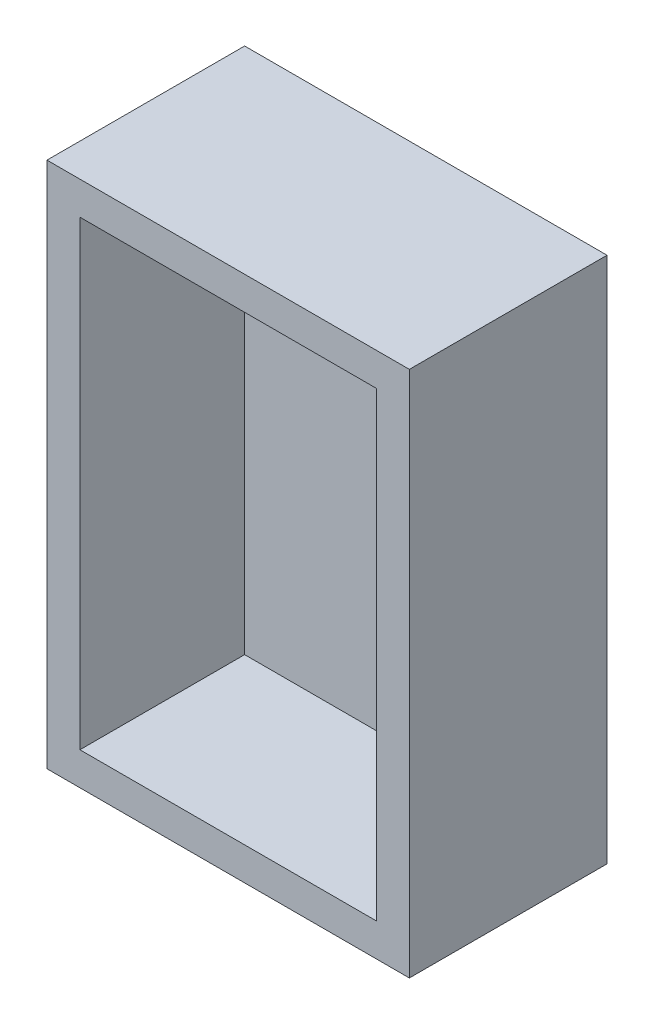
SolidWorks part; units mm, degrees
ref_plane "Front Plane" through (0, 0, 0) normal (0, 0, 1) x (1, 0, 0)
ref_plane "Top Plane" through (0, 0, 0) normal (0, 1, 0) x (1, 0, 0)
ref_plane "Right Plane" through (0, 0, 0) normal (1, 0, 0) x (0, 0, -1)
sketch "Sketch1" plane through (0, 0, 0) normal (0, 0, 1) x (1, 0, 0)
  line L1 (-11, 0) -> (11, 0)
  line L2 (-11, 0) -> (-11, 32)
  line L3 (-11, 32) -> (11, 32)
  line L4 (11, 0) -> (11, 32)
extrude "Boss-Extrude1" add sketch "Sketch1" along normal blind 12 from offset 6 offset against normal yes
sketch "Sketch2" plane through (0, 0, 0) normal (0, 0, 1) x (1, 0, 0)
  line L1 (-9, 2) -> (9, 2)
  line L2 (-9, 2) -> (-9, 30)
  line L3 (-9, 30) -> (9, 30)
  line L4 (9, 2) -> (9, 30)
extrude "Boss-Extrude2" add sketch "Sketch2" along normal blind 11 from offset 4 separate body offset against normal yes
combine bodies "Combine1" operation type subtract main body 101 bodies to subtract 102
